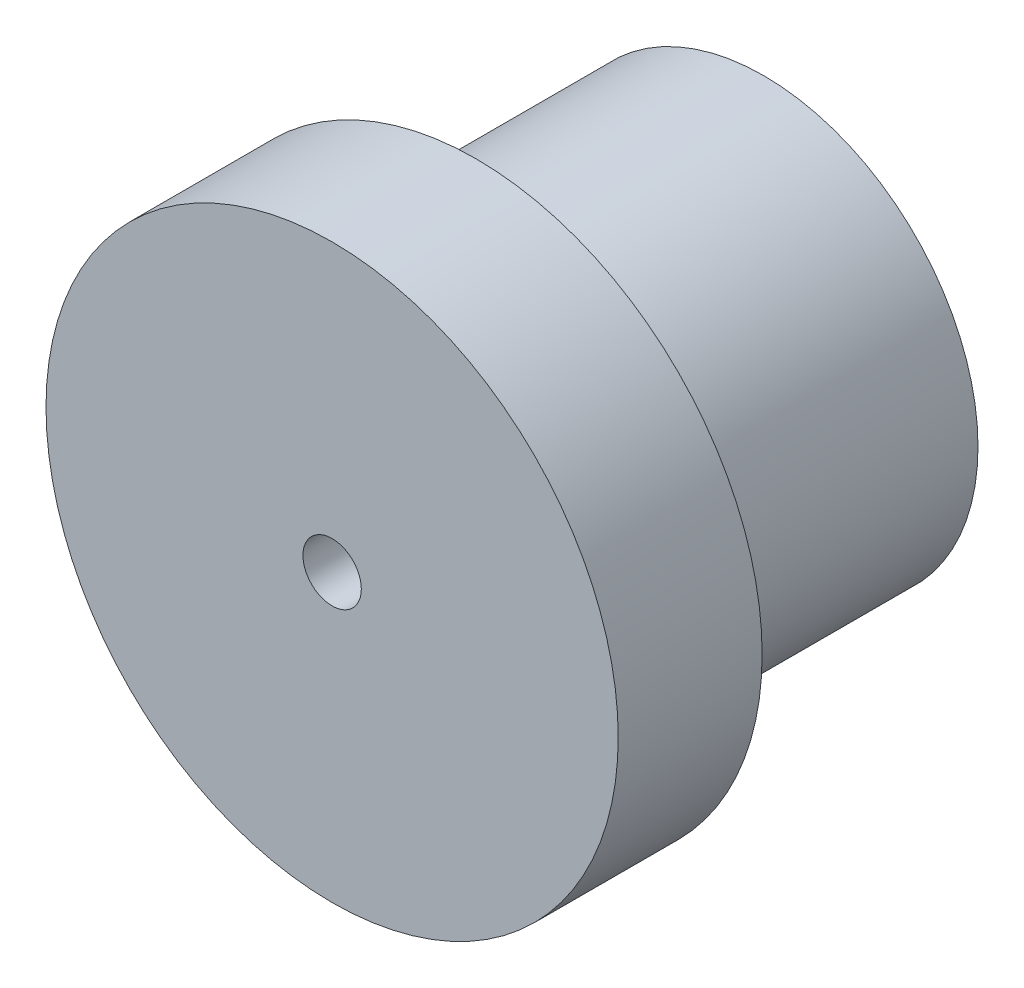
SolidWorks part; units mm, degrees
ref_plane "Front" through (0, 0, 0) normal (0, 0, 1) x (1, 0, 0)
ref_plane "Top" through (0, 0, 0) normal (0, 1, 0) x (1, 0, 0)
ref_plane "Right" through (0, 0, 0) normal (1, 0, 0) x (0, 0, -1)
sketch "Sketch1" plane through (0, 0, 0) normal (0, 0, 1) x (1, 0, 0)
  circle A0 centre (0, 0) radius 25.25
  circle A3 centre (0, 0) radius 25.4 construction
  dimension "D1" = 50.8
  dimension "D2" = 0.15
extrude "Boss-Extrude1" add sketch "Sketch1" against normal up to surface (12.7 mm away)
sketch "Sketch2" plane through (0, 0, -12.7) normal (0, 0, -1) x (-1, 0, 0)
  circle A0 centre (0, 0) radius 18.9
  circle A3 centre (0, 0) radius 19.05 construction
  dimension "D1" = 38.1
  dimension "D2" = 0.15
extrude "Boss-Extrude2" add sketch "Sketch2" along normal up to surface (25.4 mm away)
sketch "Sketch3" plane through (0, 0, -38.1) normal (0, 0, -1) x (-1, 0, 0)
  circle A0 centre (0, 0) radius 4.5
  dimension "D1" = 9
extrude "Cut-Extrude1" cut sketch "Sketch3" against normal blind 13
sketch "Sketch4" plane through (0, 0, 0) normal (0, 0, 1) x (1, 0, 0)
  line L0 (-1.5906, 2.025) -> (1.5906, 2.025)
  line L1 (0, 2.025) -> (0, -2.575) construction
  arc A0 (-1.5906, 2.025) -> (1.5906, 2.025) centre (0, 0) ccw
  arc A1 (1.5906, 2.025) -> (-1.5906, 2.025) centre (0, 0) ccw construction
  dimension "D1" = 5.15
  dimension "D2" = 4.6
extrude "Cut-Extrude2" cut sketch "Sketch4" against normal blind 20
sketch "Sketch5" plane through (0, 0, 0) normal (0, 0, 1) x (1, 0, 0)
  circle A0 centre (0, 0) radius 2.575
  dimension "D1" = 5.15
extrude "Cut-Extrude3" cut sketch "Sketch5" against normal blind 5
